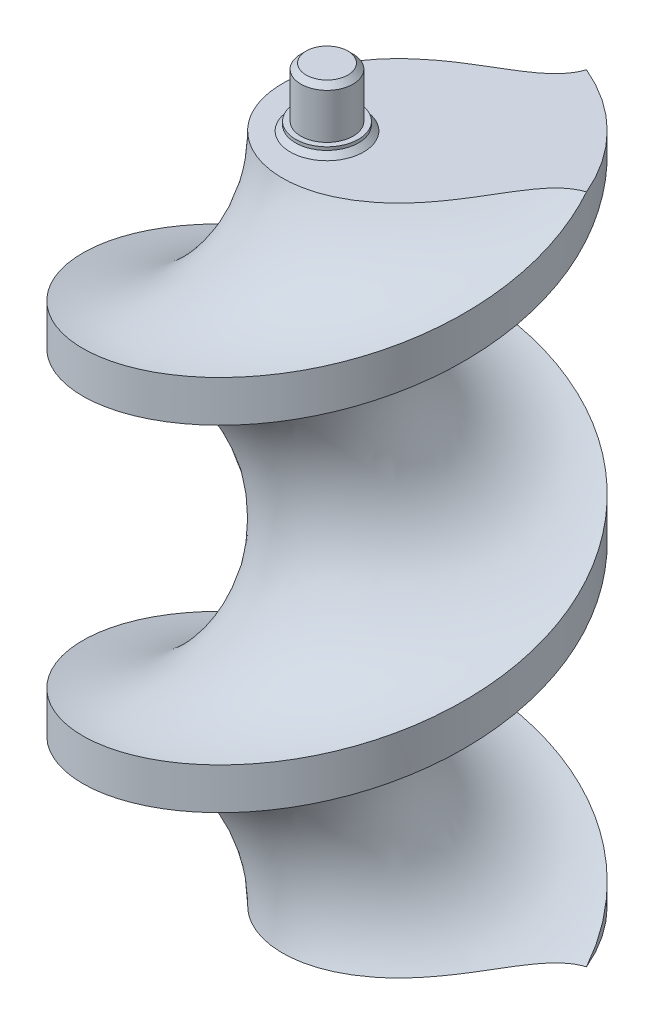
SolidWorks part; units mm, degrees
ref_plane "Front Plane" through (0, 0, 0) normal (0, 0, 1) x (1, 0, 0)
ref_plane "Top Plane" through (0, 0, 0) normal (0, 1, 0) x (1, 0, 0)
ref_plane "Right Plane" through (0, 0, 0) normal (1, 0, 0) x (0, 0, -1)
sketch "Sketch2" plane through (0, 0, 0) normal (0, 1, 0) x (1, 0, 0)
  circle A0 centre (0, 0) radius 30
  dimension "D1" = 60
extrude "Boss-Extrude1" add sketch "Sketch2" along normal mid plane 101.6
sketch "Sketch4" plane through (0, -50.8, 0) normal (0, -1, 0) x (1, 0, 0)
  circle A0 centre (0, 0) radius 30
  circle A1 centre (0, 0) radius 30 construction
curve "Helix/Spiral1" pitch 50.8 height 152.4 turns 3
sweep "Cut-Sweep1" cut path "Helix/Spiral1" align with end faces yes circular profile diameter 43 parameters "D3"=43
sketch "Sketch17" plane through (0, 50.8, 0) normal (0, 1, 0) x (1, 0, 0)
  circle A0 centre (0, 0) radius 3.95
  dimension "D1" = 7.9
extrude "Boss-Extrude2" add sketch "Sketch17" along normal blind 8.89
sketch "Sketch19" plane through (0, 50.8, 0) normal (0, 1, 0) x (1, 0, 0)
  circle A0 centre (0, 0) radius 4.7625
  dimension "D1" = 9.525
extrude "Boss-Extrude3" add sketch "Sketch19" along normal offset from surface (1.27 mm away) 7.62 up to face at (0, 59.69, 3.95)
chamfer "Chamfer1" distance 0.7937 angle 45 2 edges at (0, 50.8, 4.7625) (0, 59.69, 3.95)
sketch "Sketch20" plane through (0, -50.8, 0) normal (0, -1, 0) x (1, 0, 0)
  line L1 (-2.54, 2.032) -> (2.54, 2.032)
  line L2 (-2.54, 2.032) -> (-2.54, -2.032)
  line L3 (-2.54, -2.032) -> (2.54, -2.032)
  line L4 (2.54, 2.032) -> (2.54, -2.032)
  line L5 (-2.54, 2.032) -> (2.54, -2.032) construction
  line L6 (-2.54, -2.032) -> (2.54, 2.032) construction
  point P0 (0, 0)
  dimension "D1" = 5.08
  dimension "D2" = 4.064
extrude "Cut-Extrude1" cut sketch "Sketch20" against normal blind 7.62
sketch "Sketch21" plane through (0, -50.8, 0) normal (0, -1, 0) x (1, 0, 0)
  line L0 (2.54, 2.032) -> (-2.54, 2.032) construction
  line L1 (-2.54, -2.54) -> (2.54, -2.54)
  line L2 (-2.54, -2.54) -> (-2.54, 2.54)
  line L3 (-2.54, 2.54) -> (2.54, 2.54)
  line L4 (2.54, -2.54) -> (2.54, 2.54)
  line L5 (-2.54, -2.54) -> (2.54, 2.54) construction
  line L6 (-2.54, 2.54) -> (2.54, -2.54) construction
  point P0 (0, 0)
extrude "Cut-Extrude2" cut sketch "Sketch21" against normal blind 2.54
